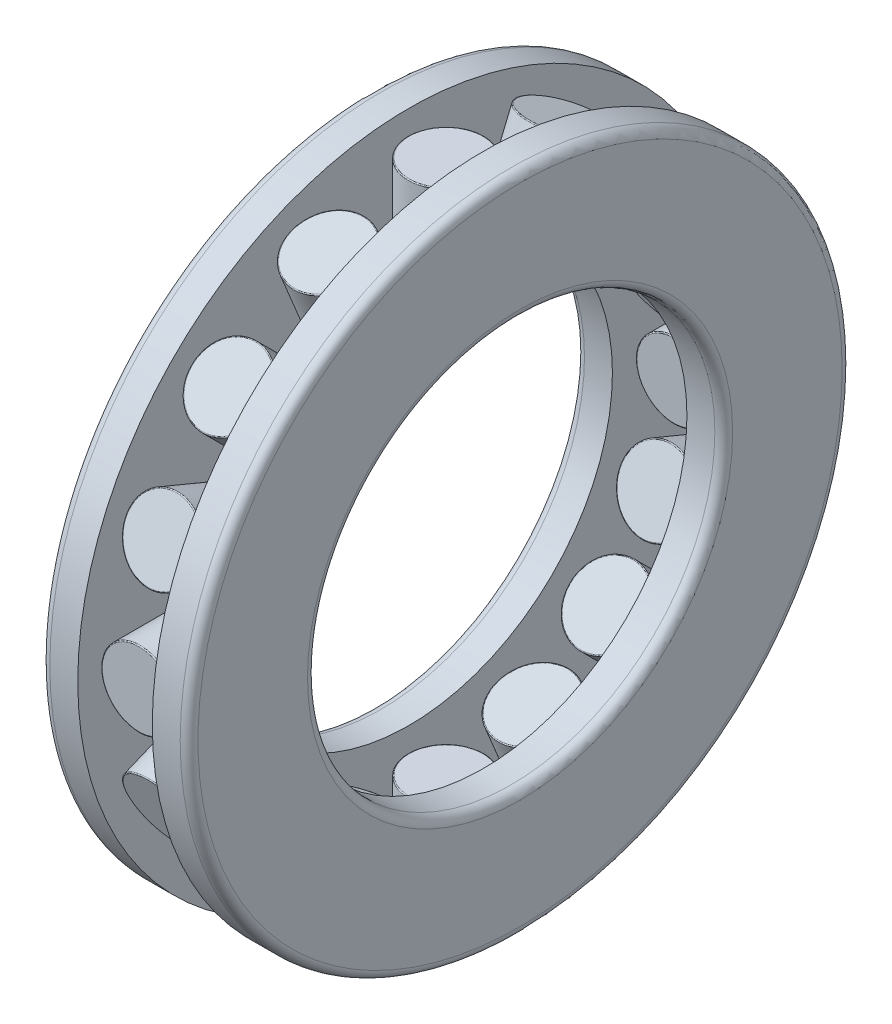
SolidWorks part; units mm, degrees
note: '?' marks a value the reader was unsure of.
ref_plane "Plane1" through (0, 0, 0) normal (0, 0, 1) x (1, 0, 0)
ref_plane "Plane2" through (0, 0, 0) normal (0, 1, 0) x (1, 0, 0)
ref_plane "Plane3" through (0, 0, 0) normal (1, 0, 0) x (0, 0, -1)
sketch "Sketch1" plane through (0, 0, 0) normal (0, 0, 1) x (1, 0, 0)
  line L0 (-6.3881, 56.7538) -> (-6.3881, 34.925)
  line L1 (-6.3881, 34.925) -> (-11.176, 34.925)
  line L2 (-12.7, 36.449) -> (-12.7, 55.2298)
  line L3 (-11.176, 56.7538) -> (-6.3881, 56.7538)
  line L4 (-34.925, 0) -> (34.925, 0) construction
  arc A0 (-11.176, 34.925) -> (-12.7, 36.449) centre (-11.176, 36.449) cw
  arc A1 (-12.7, 55.2298) -> (-11.176, 56.7538) centre (-11.176, 55.2298) cw
revolve "Base-Revolve" add sketch "Sketch1" angle 360 about L4
sketch "Sketch2" plane through (0, 0, 0) normal (0, 0, 1) x (1, 0, 0)
  line L0 (6.3151, 39.0426) -> (0, 39.0426)
  line L1 (0, 39.0426) -> (0, 52.6361)
  line L2 (0, 52.6361) -> (6.3151, 52.6361)
  line L3 (6.477, 52.4742) -> (6.477, 39.2046)
  line L4 (0, 30.5592) -> (0, 61.1195) construction
  arc A0 (6.3151, 52.6361) -> (6.477, 52.4742) centre (6.3151, 52.4742) cw
  arc A1 (6.477, 39.2046) -> (6.3151, 39.0426) centre (6.3151, 39.2046) cw
revolve "Boss-Revolve1" add sketch "Sketch2" angle 360 about L4
ref_axis "Axis1" through (-50, 0, 0) along (1, 0, 0)?
pattern_circular "CirPattern1" count 16 every 22.5 about axis through (-50, 0, 0) along (1, 0, 0)
sketch "Sketch3" plane through (0, 0, 0) normal (0, 0, 1) x (1, 0, 0)
  line L0 (6.3881, 56.7538) -> (6.3881, 34.925)
  line L1 (6.3881, 34.925) -> (11.176, 34.925)
  line L2 (12.7, 36.449) -> (12.7, 55.2298)
  line L3 (11.176, 56.7538) -> (6.3881, 56.7538)
  line L4 (-34.925, 0) -> (34.925, 0) construction
  arc A0 (11.176, 34.925) -> (12.7, 36.449) centre (11.176, 36.449) ccw
  arc A1 (12.7, 55.2298) -> (11.176, 56.7538) centre (11.176, 55.2298) ccw
revolve "Boss-Revolve2" add sketch "Sketch3" angle 360 about L4
